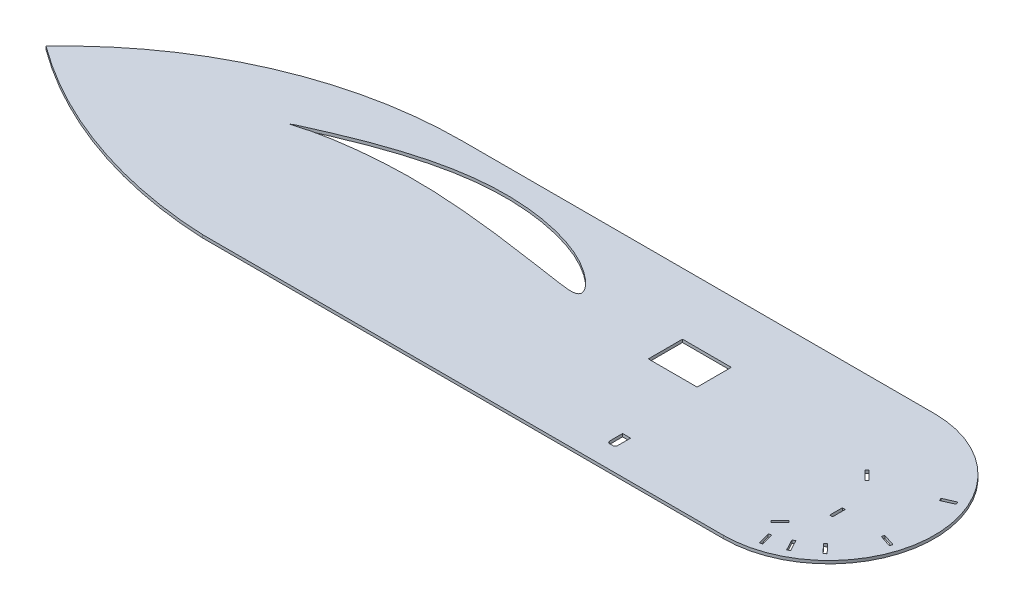
SolidWorks part; units mm, degrees
ref_plane "Front Plane" through (0, 0, 0) normal (0, 0, 1) x (1, 0, 0)
ref_plane "Top Plane" through (0, 0, 0) normal (0, 1, 0) x (1, 0, 0)
ref_plane "Right Plane" through (0, 0, 0) normal (1, 0, 0) x (0, 0, -1)
sketch "Sketch1" plane through (0, 0, 0) normal (0, 1, 0) x (1, 0, 0)
  line L0 (800, 108) -> (0, 108) construction
  line L1 (266.4083, 0) -> (800, 0)
  line L2 (0, 0) -> (0, 216) construction
  line L3 (316.2946, 216) -> (800, 216)
  line L7 (247.07, 156) -> (658.07, 156) construction
  arc A0 (800, 216) -> (800, 0) centre (800, 108) cw
  arc A2 (266.4083, 0) -> (19.4291, 86.8932) centre (286.1808, 450.645) cw
  arc A4 (19.4291, 86.8932) -> (316.2946, 216) centre (316.2946, -189.8565) cw
  dimension "D1" = 800
  dimension "D2" = 60
extrude "Boss-Extrude1" add sketch "Sketch1" along normal blind 3
sketch "Sketch2" plane through (0, 0, 0) normal (0, -1, 0) x (1, 0, 0)
  line L0 (605.07, -153) -> (605.07, 81) construction
  line L1 (655.07, -153) -> (605.07, -153)
  line L2 (655.07, -153) -> (655.07, -118)
  line L3 (655.07, -118) -> (605.07, -118)
  line L4 (823.6893, -121.2328) -> (814.4969, -130.4252)
  line L5 (814.4969, -130.4252) -> (816.6182, -132.5465)
  line L6 (816.6182, -132.5465) -> (825.8106, -123.3541)
  line L7 (825.8106, -123.3541) -> (823.6893, -121.2328)
  line L8 (823.6893, -121.2328) -> (814.4969, -130.4252)
  line L9 (814.4969, -130.4252) -> (816.6182, -132.5465)
  line L10 (816.6182, -132.5465) -> (825.8106, -123.3541)
  line L11 (825.8106, -123.3541) -> (823.6893, -121.2328)
  line L12 (605.07, -153) -> (605.07, -118)
  line L20 (824.4914, -25.0369) -> (827.9553, -12.5069)
  line L21 (827.9553, -12.5069) -> (825.0638, -11.7076)
  line L22 (825.0638, -11.7076) -> (821.5998, -24.2376)
  line L23 (821.5998, -24.2376) -> (824.4914, -25.0369)
  line L24 (824.4914, -25.0369) -> (827.9553, -12.5069)
  line L25 (827.9553, -12.5069) -> (825.0638, -11.7076)
  line L26 (825.0638, -11.7076) -> (821.5998, -24.2376)
  line L27 (821.5998, -24.2376) -> (824.4914, -25.0369)
  line L28 (839.4566, -85.3169) -> (839.4566, -72.3169)
  line L29 (839.4566, -72.3169) -> (836.4566, -72.3169)
  line L30 (836.4566, -72.3169) -> (836.4566, -85.3169)
  line L31 (836.4566, -85.3169) -> (839.4566, -85.3169)
  line L32 (839.4566, -85.3169) -> (839.4566, -72.3169)
  line L33 (839.4566, -72.3169) -> (836.4566, -72.3169)
  line L34 (836.4566, -72.3169) -> (836.4566, -85.3169)
  line L35 (836.4566, -85.3169) -> (839.4566, -85.3169)
  line L37 (212.57, -142.2618) -> (212.57, -142.2948)
  line L38 (212.57, -142.2618) -> (212.57, -142.2948)
  line L40 (658.07, -25.4734) -> (658.07, -38.6734)
  line L41 (663.77, -22.9734) -> (660.57, -22.9734)
  line L42 (666.27, -38.6734) -> (666.27, -25.4734)
  line L43 (658.07, -38.6734) -> (666.27, -38.6734)
  line L44 (658.07, -25.4734) -> (658.07, -38.6734)
  line L45 (663.77, -22.9734) -> (660.57, -22.9734)
  line L46 (666.27, -38.6734) -> (666.27, -25.4734)
  line L47 (658.07, -38.6734) -> (666.27, -38.6734)
  line L188 (878.5507, -144.2281) -> (890.4483, -149.4672) construction
  line L189 (890.4483, -149.4672) -> (891.6573, -146.7216) construction
  line L190 (891.6573, -146.7216) -> (879.7597, -141.4825) construction
  line L191 (879.7597, -141.4825) -> (878.5507, -144.2281) construction
  line L192 (882.697, -82.6247) -> (895.0571, -78.5963) construction
  line L193 (895.0571, -78.5963) -> (894.1274, -75.744) construction
  line L194 (894.1274, -75.744) -> (881.7674, -79.7724) construction
  line L195 (881.7674, -79.7724) -> (882.697, -82.6247) construction
  line L196 (860.5167, -46.1904) -> (869.449, -36.745) construction
  line L197 (869.449, -36.745) -> (867.2693, -34.6838) construction
  line L198 (867.2693, -34.6838) -> (858.337, -44.1291) construction
  line L199 (858.337, -44.1291) -> (860.5167, -46.1904) construction
  line L200 (841.8546, -32.2973) -> (847.9464, -20.813) construction
  line L201 (847.9464, -20.813) -> (845.2962, -19.4072) construction
  line L202 (845.2962, -19.4072) -> (839.2044, -30.8915) construction
  line L203 (839.2044, -30.8915) -> (841.8546, -32.2973) construction
  line L204 (822.4089, -44.7346) -> (813.2165, -35.5422) construction
  line L205 (813.2165, -35.5422) -> (811.0952, -37.6635) construction
  line L206 (811.0952, -37.6635) -> (820.2876, -46.8559) construction
  line L207 (820.2876, -46.8559) -> (822.4089, -44.7346) construction
  line L208 (878.5507, -144.2281) -> (890.4483, -149.4672)
  line L209 (890.4483, -149.4672) -> (891.6573, -146.7216)
  line L210 (891.6573, -146.7216) -> (879.7597, -141.4825)
  line L211 (879.7597, -141.4825) -> (878.5507, -144.2281)
  line L212 (882.697, -82.6247) -> (895.0571, -78.5963)
  line L213 (895.0571, -78.5963) -> (894.1274, -75.744)
  line L214 (894.1274, -75.744) -> (881.7674, -79.7724)
  line L215 (881.7674, -79.7724) -> (882.697, -82.6247)
  line L216 (860.5167, -46.1904) -> (869.449, -36.745)
  line L217 (869.449, -36.745) -> (867.2693, -34.6838)
  line L218 (867.2693, -34.6838) -> (858.337, -44.1291)
  line L219 (858.337, -44.1291) -> (860.5167, -46.1904)
  line L220 (841.8546, -32.2973) -> (847.9464, -20.813)
  line L221 (847.9464, -20.813) -> (845.2962, -19.4072)
  line L222 (845.2962, -19.4072) -> (839.2044, -30.8915)
  line L223 (839.2044, -30.8915) -> (841.8546, -32.2973)
  line L224 (822.4089, -44.7346) -> (813.2165, -35.5422)
  line L225 (813.2165, -35.5422) -> (811.0952, -37.6635)
  line L226 (811.0952, -37.6635) -> (820.2876, -46.8559)
  line L227 (820.2876, -46.8559) -> (822.4089, -44.7346)
  arc A2 (660.57, -22.9734) -> (658.07, -25.4734) centre (660.57, -25.4734) ccw
  arc A3 (666.27, -25.4734) -> (663.77, -22.9734) centre (663.77, -25.4734) ccw
  arc A4 (660.57, -22.9734) -> (658.07, -25.4734) centre (660.57, -25.4734) ccw
  arc A5 (666.27, -25.4734) -> (663.77, -22.9734) centre (663.77, -25.4734) ccw
  spline S1 degree 3 poles (-935.9633, -1778.8288) (190.5889, -95.3438) (194.6064, -131.763) (215.6642, -144.2206) (218.7234, -145.7779) (222.7838, -147.5804) (227.7591, -149.7808) (233.6732, -152.3729) (243.3346, -156.474) (254.0716, -160.9286) (265.8113, -165.5514) (275.5598, -169.1926) (285.8203, -172.7897) (300.2132, -177.4429) (315.0475, -181.6144) (330.2168, -185.0782) (341.7168, -187.2628) (353.2384, -188.9705) (364.7498, -190.1898) (376.2222, -190.8893) (387.6115, -191.0869) (398.8538, -190.7647) (413.4214, -189.6963) (427.5808, -187.7) (441.1954, -184.8275) (450.8219, -182.3197) (459.9489, -179.4697) (468.5117, -176.2876) (476.4536, -172.8247) (483.7151, -169.1289) (490.2481, -165.2848) (496.0197, -161.4069) (500.998, -157.5857) (505.1476, -153.8841) (508.4473, -150.3827) (510.8522, -147.1808) (512.2305, -144.519) (512.6724, -142.438) (512.366, -140.694) (510.8363, -139.2679) (508.3008, -138.6046) (504.9907, -138.3969) (500.8451, -138.6329) (495.8864, -139.207) (490.1274, -140.0338) (483.6007, -141.0142) (476.346, -142.082) (468.4189, -143.2709) (459.8696, -144.553) (447.4042, -146.414) (434.3028, -148.292) (413.2306, -151.0803) (394.9165, -153.1705) (372.4131, -155.1852) (353.2786, -156.4974) (334.1039, -157.1205) (318.8375, -157.1193) (307.5693, -156.8631) (296.5448, -156.3424) (285.8536, -155.5986) (275.5863, -154.6546) (265.8296, -153.5569) (256.6735, -152.3128) (248.205, -150.9585) (240.5101, -149.5233) (233.6661, -148.0641) (227.7356, -146.6296) (222.7715, -145.2056) (218.7746, -143.9126) (215.7248, -142.9952) (193.3721, -137.343) (166.6151, -157.487) (567.9657, 1824.9991) knots -0.10608 -0.10608 -0.10608 -0.10608 0.001413 0.005226 0.010781 0.017816 0.026461 0.036791 0.048686 0.076639 0.092363 0.109003 0.126387 0.144339 0.181313 0.200023 0.218713 0.237261 0.255692 0.274037 0.292193 0.310133 0.327788 0.362002 0.378421 0.394287 0.409543 0.424114 0.437938 0.450942 0.463044 0.474154 0.484165 0.493024 0.500713 0.507126 0.51213 0.514904 0.517171 0.520262 0.524245 0.529498 0.536092 0.544061 0.553363 0.563905 0.575615 0.58842 0.602227 0.616944 0.648676 0.665501 0.718564 0.736789 0.773513 0.810245 0.828489 0.846493 0.864125 0.881249 0.897725 0.913415 0.928184 0.941897 0.954411 0.965603 0.97535 0.983576 0.990285 0.995433 0.9988 1.100441 1.100441 1.100441 1.100441 only from (212.57, -142.2948) to (212.57, -142.2618)
  spline S2 degree 3 poles (212.57, -142.2948) (212.8151, -142.4601) (213.7215, -143.0713) (215.6642, -144.2206) (218.7234, -145.7779) (222.7838, -147.5804) (227.7591, -149.7808) (233.6732, -152.3729) (243.3346, -156.474) (254.0716, -160.9286) (265.8113, -165.5514) (275.5598, -169.1926) (285.8203, -172.7897) (300.2132, -177.4429) (315.0475, -181.6144) (330.2168, -185.0782) (341.7168, -187.2628) (353.2384, -188.9705) (364.7498, -190.1898) (376.2222, -190.8893) (387.6115, -191.0869) (398.8538, -190.7647) (413.4214, -189.6963) (427.5808, -187.7) (441.1954, -184.8275) (450.8219, -182.3197) (459.9489, -179.4697) (468.5117, -176.2876) (476.4536, -172.8247) (483.7151, -169.1289) (490.2481, -165.2848) (496.0197, -161.4069) (500.998, -157.5857) (505.1476, -153.8841) (508.4473, -150.3827) (510.8522, -147.1808) (512.2305, -144.519) (512.6724, -142.438) (512.366, -140.694) (510.8363, -139.2679) (508.3008, -138.6046) (504.9907, -138.3969) (500.8451, -138.6329) (495.8864, -139.207) (490.1274, -140.0338) (483.6007, -141.0142) (476.346, -142.082) (468.4189, -143.2709) (459.8696, -144.553) (447.4042, -146.414) (434.3028, -148.292) (413.2306, -151.0803) (394.9165, -153.1705) (372.4131, -155.1852) (353.2786, -156.4974) (334.1039, -157.1205) (318.8375, -157.1193) (307.5693, -156.8631) (296.5448, -156.3424) (285.8536, -155.5986) (275.5863, -154.6546) (265.8296, -153.5569) (256.6735, -152.3128) (248.205, -150.9585) (240.5101, -149.5233) (233.6661, -148.0641) (227.7356, -146.6296) (222.7715, -145.2056) (218.7746, -143.9126) (215.7248, -142.9952) (213.7534, -142.4967) (212.8162, -142.3107) (212.57, -142.2618) knots 0 0 0 0 0.001413 0.005226 0.010781 0.017816 0.026461 0.036791 0.048686 0.076639 0.092363 0.109003 0.126387 0.144339 0.181313 0.200023 0.218713 0.237261 0.255692 0.274037 0.292193 0.310133 0.327788 0.362002 0.378421 0.394287 0.409543 0.424114 0.437938 0.450942 0.463044 0.474154 0.484165 0.493024 0.500713 0.507126 0.51213 0.514904 0.517171 0.520262 0.524245 0.529498 0.536092 0.544061 0.553363 0.563905 0.575615 0.58842 0.602227 0.616944 0.648676 0.665501 0.718564 0.736789 0.773513 0.810245 0.828489 0.846493 0.864125 0.881249 0.897725 0.913415 0.928184 0.941897 0.954411 0.965603 0.97535 0.983576 0.990285 0.995433 0.9988 1 1 1 1
  dimension "D6" = 35
  dimension "D1" = 0
  dimension "D2" = 0
  dimension "D3" = 0
  dimension "D4" = 0
  dimension "D5" = 0
extrude "Cut-Extrude1" cut sketch "Sketch2" against normal through all
